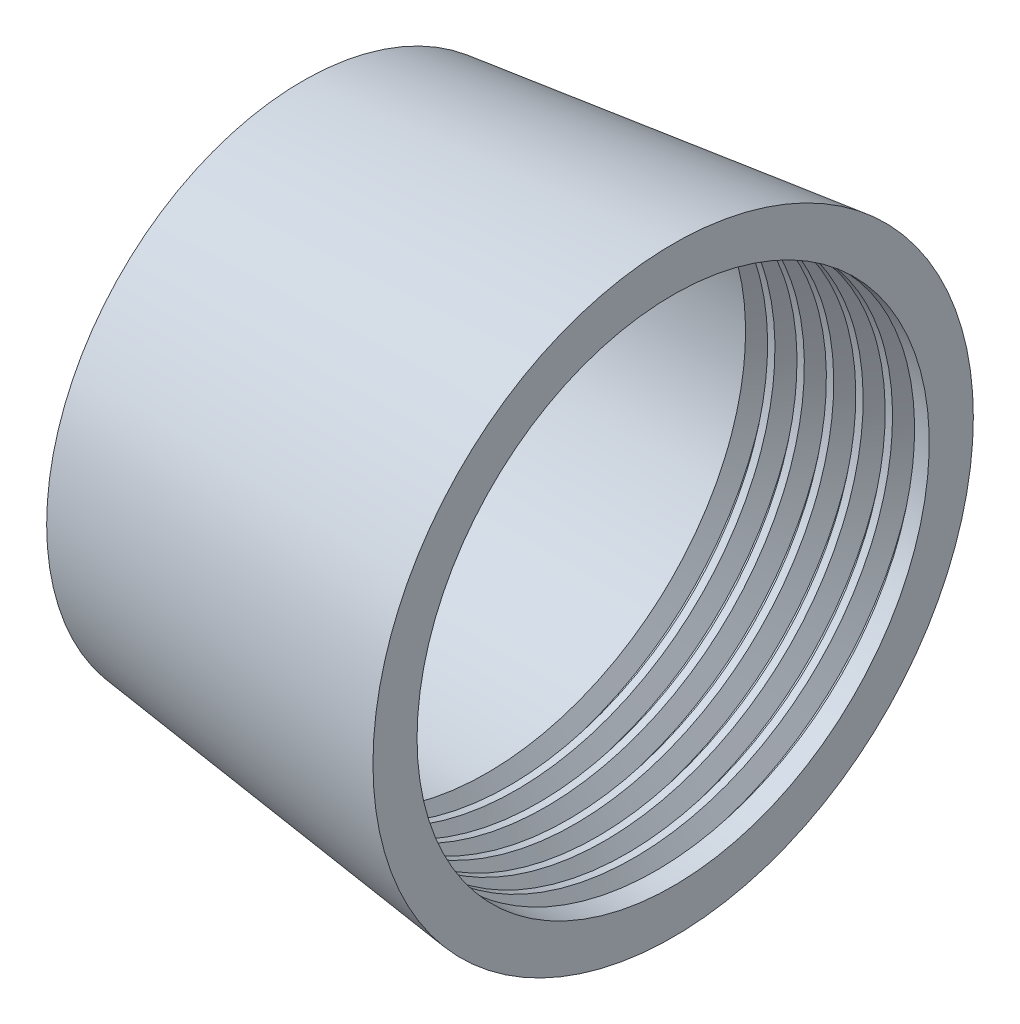
SolidWorks part; units mm, degrees
ref_plane "Front Plane" through (0, 0, 0) normal (0, 0, 1) x (1, 0, 0)
ref_plane "Top Plane" through (0, 0, 0) normal (0, 1, 0) x (1, 0, 0)
ref_plane "Right Plane" through (0, 0, 0) normal (1, 0, 0) x (0, 0, -1)
sketch "Sketch1" plane through (0, 0, 0) normal (0, 0, 1) x (1, 0, 0)
  line L0 (0, 0) -> (33.1466, 0) construction
  line L1 (26.67, 21.6154) -> (0, 18.4404)
  line L2 (0, 18.4404) -> (26.67, 18.4404)
  line L3 (26.67, 18.4404) -> (26.67, 21.6154)
  line L4 (0, 0) -> (0, 18.4404) construction
  dimension "D1" = 3.175
  dimension "D2" = 26.67
  dimension "D3" = 18.4404
revolve "Revolve1" add sketch "Sketch1" angle 360 about L0
thread "Thread1" pitch 2.1167 method cut profile "Thread Profile1" start angle 0, offset 0, length 12.7, pitch 2.1167, diameter 36.8808
ref_plane "Plane1" through (26.67, 0, 18.4404) normal (0, -1, 0) x (0, 0, 1)
sketch "Thread Profile1" plane through (26.67, 0, 18.4404) normal (0, -1, 0) x (0, 0, 1)
  line L0 (0, 0) -> (0, 2.1167) construction
  line L1 (0, 0) -> (1.1457, 0.6615)
  line L2 (1.1457, 0.6615) -> (1.1457, 0.926)
  line L3 (1.1457, 0.926) -> (0, 1.5875)
  line L4 (1.1457, 0.7937) -> (0, 0.7937) construction
  line L11 (0, 0) -> (0, 1.5875)
  point P2 (0, 0)
  dimension "Pitch" = 2.1167
  dimension "Profile_Angle" = 60
  dimension "Profile_Land" = 0.2646
  dimension "Profile_Height" = 1.1457
